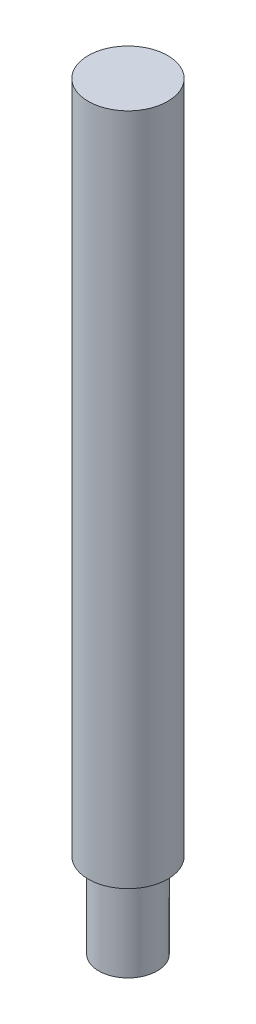
SolidWorks part; units mm, degrees
material "6061 Alloy"
ref_plane "Front Plane" through (0, 0, 0) normal (0, 0, 1) x (1, 0, 0)
ref_plane "Top Plane" through (0, 0, 0) normal (0, 1, 0) x (1, 0, 0)
ref_plane "Right Plane" through (0, 0, 0) normal (1, 0, 0) x (0, 0, -1)
sketch "Sketch1" plane through (0, 0, 0) normal (0, 1, 0) x (1, 0, 0)
  circle A0 centre (0, 0) radius 2.3813
  dimension "D1" = 4.7625
extrude "Boss-Extrude1" add sketch "Sketch1" along normal blind 40.3733
sketch "Sketch2" plane through (0, 0, 0) normal (0, -1, 0) x (1, 0, 0)
  circle A0 centre (0, 0) radius 1.7526
  dimension "D1" = 3.5052
extrude "Boss-Extrude2" add sketch "Sketch2" along normal blind 5.08
